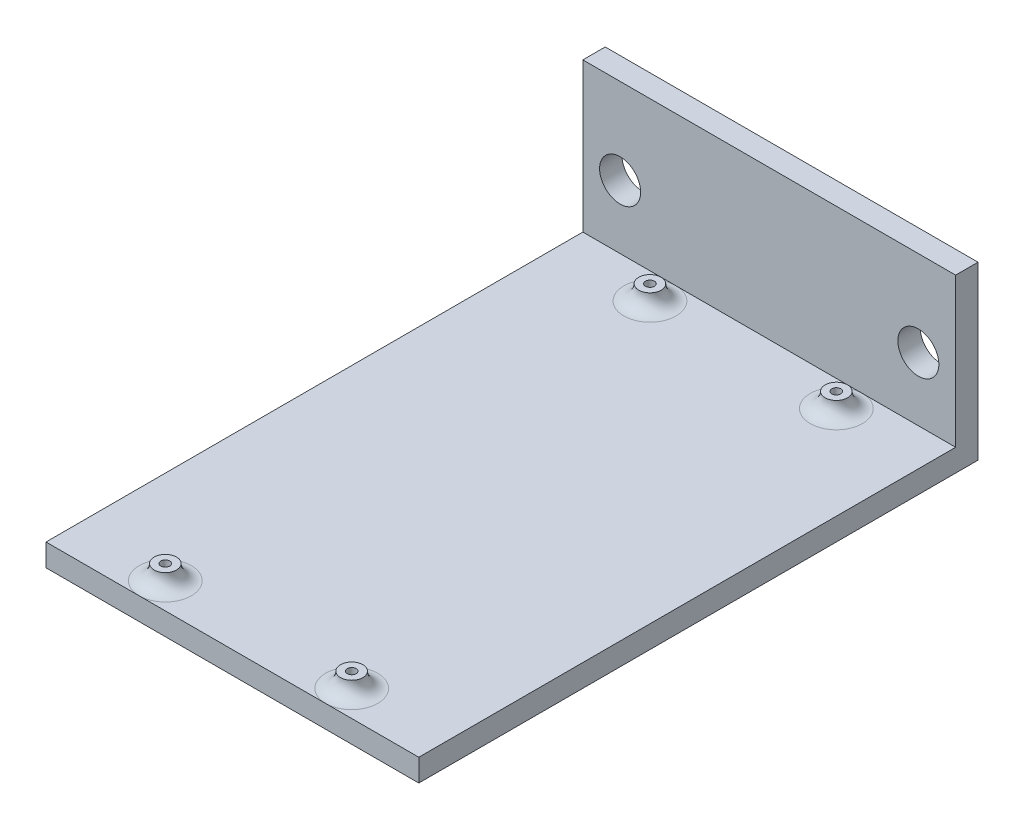
SolidWorks part; units mm, degrees
ref_plane "Front Plane" through (0, 0, 0) normal (0, 0, 1) x (1, 0, 0)
ref_plane "Top Plane" through (0, 0, 0) normal (0, 1, 0) x (1, 0, 0)
ref_plane "Right Plane" through (0, 0, 0) normal (1, 0, 0) x (0, 0, -1)
sketch "Sketch1" plane through (0, 0, 0) normal (0, 1, 0) x (1, 0, 0)
  line L1 (-25, 37.5) -> (25, 37.5)
  line L2 (-25, 37.5) -> (-25, -37.5)
  line L3 (-25, -37.5) -> (25, -37.5)
  line L4 (25, 37.5) -> (25, -37.5)
  line L5 (-25, 37.5) -> (25, -37.5) construction
  line L6 (-25, -37.5) -> (25, 37.5) construction
  point P0 (0, 0)
  dimension "D1" = 75
  dimension "D2" = 50
extrude "Boss-Extrude1" add sketch "Sketch1" along normal blind 3
sketch "Sketch2" plane through (0, 3, 0) normal (0, 1, 0) x (1, 0, 0)
  line L0 (25, -37.5) -> (25, 37.5) construction
  line L1 (-25, 37.5) -> (25, 37.5)
  line L2 (-25, 37.5) -> (-25, 34.5)
  line L3 (-25, 34.5) -> (25, 34.5)
  line L4 (25, 37.5) -> (25, 34.5)
  dimension "D1" = 3
extrude "Boss-Extrude2" add sketch "Sketch2" along normal blind 20
sketch "Sketch4" plane through (0, 0, -37.5) normal (0, 0, -1) x (-1, 0, 0)
  line L0 (0, 23) -> (0, 0) construction
  line L1 (-25, 23) -> (25, 23) construction
  line L2 (-20, 11.5) -> (20, 11.5) construction
  line L3 (-25, 23) -> (-25, 0) construction
  point P8 (0, 11.5)
  dimension "D1" = 5
hole_wizard "M5 Clearance Hole1" positions "3DSketch1" profile "Sketch5" hole size "M5" standard "ANSI Metric" end condition through all
sketch3d "3DSketch1"
  point P0 (20, 11.5, -37.5)
  point P3 (-20, 11.5, -37.5)
  point P6 (-94.6634, 64.2229, 0)
sketch "Sketch5" plane through (20, 11.5, -37.5) normal (1, 0, 0) x (0, 1, 0)
  line L0 (0, 0) -> (0, 75)
  line L1 (0, 75) -> (2.75, 75)
  line L2 (2.75, 75) -> (2.75, 0)
  line L5 (2.75, 0) -> (0, 0)
  line L11 (0, -6.35) -> (0, 107.95) construction
  dimension "Thru Hole Dia." = 5.5
  dimension "Thru Hole Depth" = 75
sketch "Sketch6" plane through (0, 3, 0) normal (0, 1, 0) x (1, 0, 0)
  line L0 (0, 34.5) -> (0, -37.5) construction
  line L1 (-25, 34.5) -> (25, 34.5) construction
  line L2 (-25, -37.5) -> (25, -37.5) construction
  line L4 (-12.5, 31) -> (12.5, 31) construction
  line L5 (-12.5, 31) -> (-12.5, -34) construction
  line L6 (-12.5, -34) -> (12.5, -34) construction
  line L7 (12.5, 31) -> (12.5, -34) construction
  line L8 (-12.5, 31) -> (12.5, -34) construction
  line L9 (-12.5, -34) -> (12.5, 31) construction
  circle A0 centre (-12.5, 31) radius 1.5
  circle A1 centre (12.5, 31) radius 1.5
  circle A2 centre (12.5, -34) radius 1.5
  circle A3 centre (-12.5, -34) radius 1.5
  point P6 (0, -1.5)
  dimension "D3" = 3
  dimension "D1" = 25
  dimension "D2" = 65
extrude "Boss-Extrude3" add sketch "Sketch6" along normal blind 2
sketch "Sketch7" plane through (0, 5, 0) normal (0, 1, 0) x (1, 0, 0)
  circle A0 centre (-12.5, 31) radius 0.6
  circle A1 centre (12.5, 31) radius 0.6
  circle A2 centre (12.5, -34) radius 0.6
  circle A3 centre (-12.5, -34) radius 0.6
  dimension "D1" = 1.2
extrude "Cut-Extrude1" cut sketch "Sketch7" against normal up to next
fillet "Fillet1" radius 2 4 edges at (12.5, 3, 35.5) (-12.5, 3, 35.5) (12.5, 3, -29.5) (-12.5, 3, -29.5)
